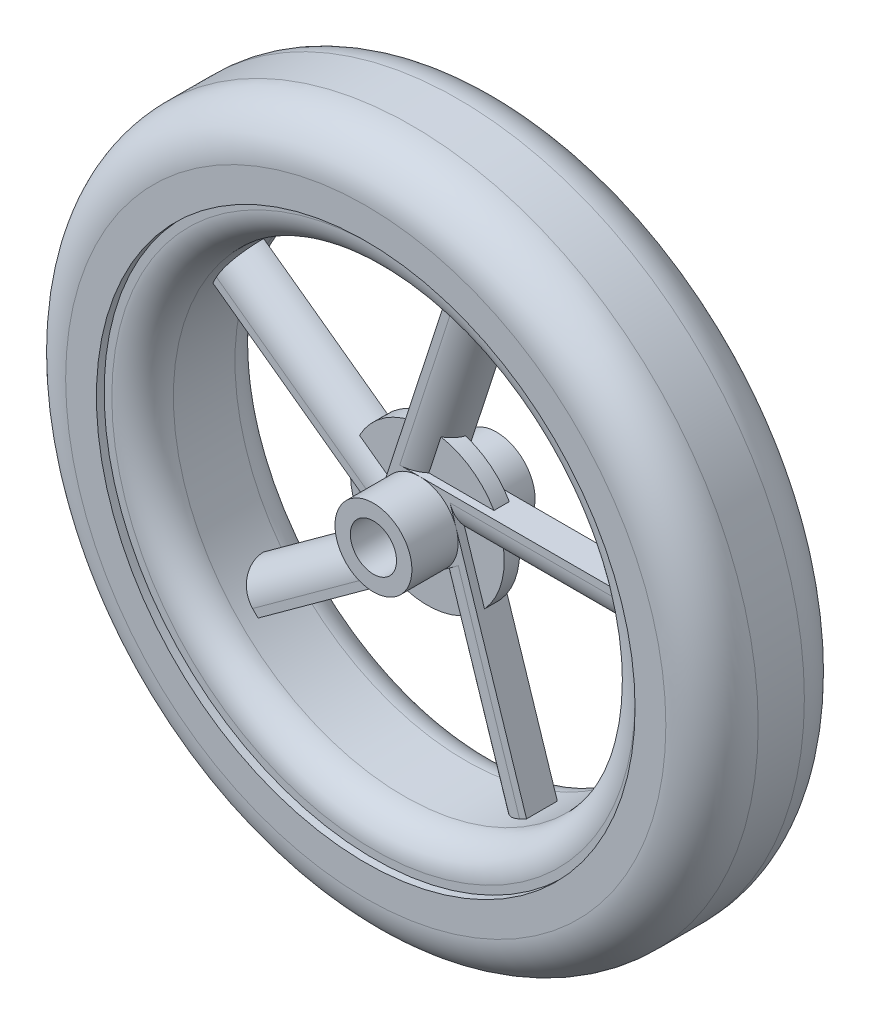
SolidWorks part; units mm, degrees
ref_plane "Front Plane" through (0, 0, 0) normal (0, 0, 1) x (1, 0, 0)
ref_plane "Top Plane" through (0, 0, 0) normal (0, 1, 0) x (1, 0, 0)
ref_plane "Right Plane" through (0, 0, 0) normal (1, 0, 0) x (0, 0, -1)
sketch "Sketch2" plane through (0, 0, 0) normal (0, 0, 1) x (1, 0, 0)
  circle A0 centre (0, 0) radius 1.5
  circle A1 centre (0, 0) radius 2.5
extrude "Boss-Extrude1" add sketch "Sketch2" along normal mid plane 8
sketch "Sketch3" plane through (0, 0, 0) normal (0, 0, 1) x (1, 0, 0)
  circle A0 centre (0, 0) radius 15
  circle A1 centre (0, 0) radius 17.5
  dimension "D1" = 30
  dimension "D2" = 35
extrude "Boss-Extrude2" add sketch "Sketch3" along normal mid plane 8 separate body
sketch "Sketch4" plane through (0, 0, 0) normal (0, 0, 1) x (1, 0, 0)
  line L0 (0.8123, 2.5) -> (14.7902, 2.5)
  line L1 (2.6287, 0) -> (15, 0)
  line L2 (2.6287, 0) -> (6.9481, -13.2938)
  line L3 (0.8123, -2.5) -> (4.6353, -14.2658)
  line L4 (0.8123, -2.5) -> (-10.4961, -10.716)
  line L5 (-2.1266, -1.5451) -> (-12.1353, -8.8168)
  line L6 (-2.1266, -1.5451) -> (-13.435, 6.6709)
  line L7 (-2.1266, 1.5451) -> (-12.1353, 8.8168)
  line L8 (-2.1266, 1.5451) -> (2.1928, 14.8389)
  line L9 (0.8123, 2.5) -> (4.6353, 14.2658)
  circle A0 centre (0, 0) radius 2.5
  circle A1 centre (0, 0) radius 15 construction
  arc A2 (15, 0) -> (14.7902, 2.5) centre (0, 0) ccw
  arc A3 (4.6353, -14.2658) -> (6.9481, -13.2938) centre (0, 0) ccw
  arc A4 (-12.1353, -8.8168) -> (-10.4961, -10.716) centre (0, 0) ccw
  arc A5 (-12.1353, 8.8168) -> (-13.435, 6.6709) centre (0, 0) ccw
  arc A6 (4.6353, 14.2658) -> (2.1928, 14.8389) centre (0, 0) ccw
  point P28 (0, 0)
  dimension "D1" = 5
extrude "Boss-Extrude3" add sketch "Sketch4" along normal mid plane 2
sketch "Sketch5" plane through (0, 0, 0) normal (0, 0, 1) x (1, 0, 0)
  circle A0 centre (0, 0) radius 5
  circle A1 centre (0, 0) radius 2.5
extrude "Boss-Extrude4" add sketch "Sketch5" along normal mid plane 1
fillet "Fillet1" radius 2 2 edges at (15, 0, -4) (15, 0, 4)
fillet "Fillet2" radius 2 5 edges at (-7.1309, -5.1809, 1) (2.7238, -8.3829, 1) (8.8143, 0, 1) (2.7238, 8.3829, 1) (-7.1309, 5.1809, 1)
sketch "Sketch6" plane through (0, 0, 0) normal (0, 0, 1) x (1, 0, 0)
  circle A0 centre (0, 0) radius 17.5
  circle A1 centre (0, 0) radius 22.5
extrude "Boss-Extrude5" add sketch "Sketch6" along normal mid plane 9
fillet "Fillet3" radius 3 2 edges at (22.5, 0, -4.5) (22.5, 0, 4.5)
